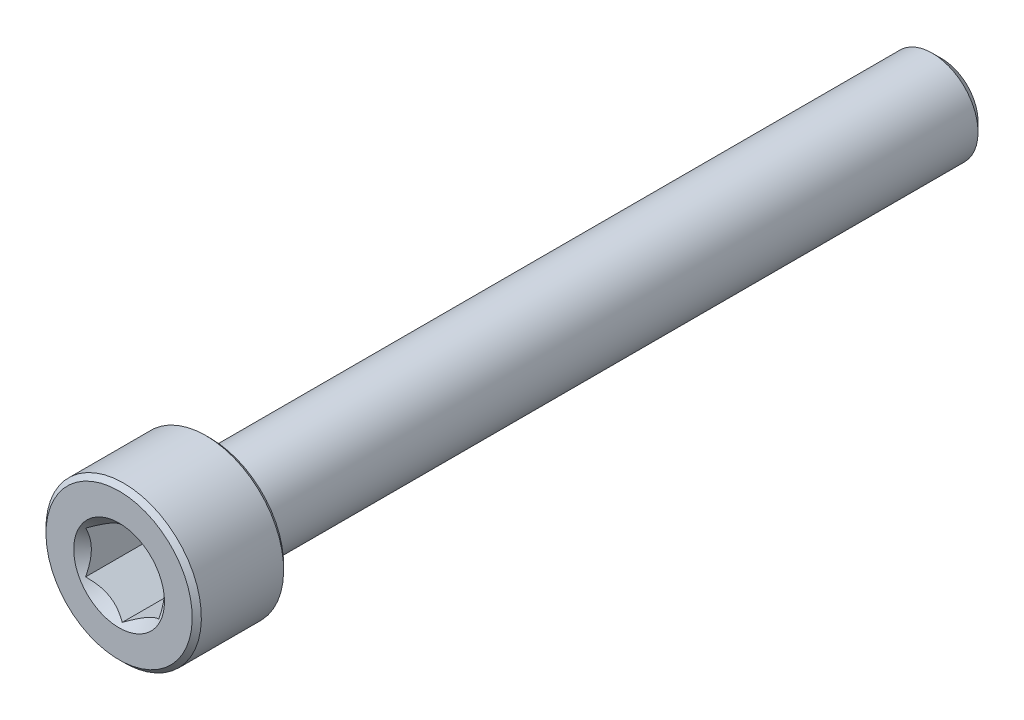
SolidWorks part; units mm, degrees
ref_plane "Front Plane" through (0, 0, 0) normal (0, 0, 1) x (1, 0, 0)
ref_plane "Top Plane" through (0, 0, 0) normal (0, 1, 0) x (1, 0, 0)
ref_plane "Right Plane" through (0, 0, 0) normal (1, 0, 0) x (0, 0, -1)
sketch "Sketch1" plane through (0, 0, 0) normal (1, 0, 0) x (0, 0, -1)
  line L0 (-22.5, 0) -> (22.5, 0) construction
  line L1 (22.5, 0) -> (22.5, 1.9804) construction
  line L2 (22.5, 1.9804) -> (21.9804, 2.5) construction
  line L3 (21.9804, 2.5) -> (21.9, 2.5) construction
  line L4 (21.9, 2.5) -> (-17.5, 2.5) construction
  line L5 (-17.5, 2.5) -> (-17.5, 4.25) construction
  line L6 (-17.5, 4.25) -> (-22.5, 4.25) construction
  line L7 (-22.5, 4.25) -> (-22.5, 0) construction
  line L8 (22.5, 1.9804) -> (22.5, 2.5) construction
  line L9 (22.45, 2.5866) -> (22.85, 1.8938) construction
  line L10 (22.85, 1.8938) -> (23.25, 2.5866) construction
  line L11 (23.25, 2.5866) -> (22.45, 2.5866) construction
  line L12 (22.85, 2.5866) -> (22.85, 2.5) construction
  line L13 (22.85, 1.8938) -> (22.85, 1.9804) construction
  line L14 (22.8, 1.9804) -> (22.9, 1.9804) construction
  line L15 (22.5, 2.5) -> (23.2, 2.5) construction
  line L16 (22.475, 2.5433) -> (23.225, 2.5433) construction
  line L17 (22.5, 0) -> (22.5, -2.5) construction
  line L18 (-17.75, 4.25) -> (-17.5, 4) construction
  line L19 (-22.25, 4.25) -> (-22.5, 4) construction
  line L20 (-17.5, 2.5) -> (-17.5, 0) construction
  line L21 (-17.5, 1.25) -> (-4.1667, 1.25) construction
  line L22 (-4.1667, 1.25) -> (9.1667, 1.25) construction
  line L23 (9.1667, 1.25) -> (22.5, 1.25) construction
  line L24 (-4.1667, 1.25) -> (-4.1667, 2.5) construction
  line L25 (-4.1667, 2.5) -> (-4.1667, 4.25) construction
  line L26 (9.1667, 1.25) -> (9.1667, 4.25) construction
  point P0 (-22.5, 2)
  point P3 (20.5, 2.5)
  point P4 (0, 0)
  point P18 (9.1667, 2.5)
  point P22 (22.85, 1.9804)
  point P24 (21.9, 2.5)
  point P25 (22.85, 2.5)
  point P28 (22.85, 2.5433)
  point P29 (20.5, -2.5)
  point P30 (-4.1667, 2.5)
  point P31 (-20, 4.25)
  point P37 (-18.375, 4.25)
  point P38 (-22.125, 4.25)
  point P45 (-4.1667, 1.25)
  point P46 (9.1667, 1.25)
  dimension "D2" = 0.1
  dimension "D7" = 0.25
  dimension "D8" = 0.25
  dimension "D9" = 0.25
  dimension "D10" = 0.125
  dimension "D11" = 0.625
  dimension "Drive Size" = 4
  dimension "Head Diameter" = 8.5
  dimension "Head Height" = 5
  dimension "Thread Pitch" = 0.8
  dimension "Thread Dia" = 5
  dimension "Length" = 40
  dimension "D12" = 0.6
  dimension "D4" = 2
  dimension "D3" = 45
sketch "Sketch2" plane through (0, 0, 0) normal (1, 0, 0) x (0, 0, -1)
  line L0 (-22.5, 0) -> (-22.5, 4)
  line L1 (-22.25, 4.25) -> (-17.75, 4.25)
  line L2 (-17.5, 4) -> (-17.5, 2.75)
  line L4 (21.9804, 2.5) -> (22.5, 1.9804)
  line L5 (22.5, 1.9804) -> (22.5, 0)
  line L6 (-17.5, 4.25) -> (-22.5, 4.25) construction
  line L7 (22.5, 0) -> (-22.5, 0)
  line L8 (-22.25, 4.25) -> (-22.5, 4) construction
  line L10 (-22.25, 4.25) -> (-22.5, 4)
  line L14 (-17.75, 4.25) -> (-17.5, 4) construction
  line L16 (-17.75, 4.25) -> (-17.5, 4)
  line L17 (-17.5, 2.5) -> (-17.5, 4.25) construction
  line L19 (-17.25, 2.5) -> (21.9804, 2.5)
  line L20 (21.9, 2.5) -> (-17.5, 2.5) construction
  arc A1 (-17.5, 2.75) -> (-17.25, 2.5) centre (-17.25, 2.75) ccw
  dimension "D3" = 0.25
revolve "Revolve1" add sketch "Sketch2" angle 360 about L7
sketch "Sketch3" plane through (0, 0, 22.5) normal (0, 0, 1) x (1, 0, 0)
  line L1 (2, -1.1547) -> (2, 1.1547)
  line L2 (2, 1.1547) -> (0, 2.3094)
  line L3 (0, 2.3094) -> (-2, 1.1547)
  line L4 (-2, 1.1547) -> (-2, -1.1547)
  line L5 (-2, -1.1547) -> (0, -2.3094)
  line L6 (0, -2.3094) -> (2, -1.1547)
  circle A0 centre (0, 0) radius 2 construction
  circle A1 centre (0, 0) radius 4.25 construction
  circle A2 centre (0, 0) radius 4.25 construction
  circle A3 centre (0, 0) radius 2.3094 construction
  point P13 (0, 0)
  dimension "D1" = 4.6188
extrude "Cut-Extrude1" cut sketch "Sketch3" against normal offset from surface (4 mm away) 1 up to face at (0, 4, 17.5)
sketch "Sketch4" plane through (0, 0, 22.5) normal (0, 0, 1) x (1, 0, 0)
  circle A0 centre (0, 0) radius 2.4826
  dimension "D1" = 4.9652
extrude "Cut-Extrude2" cut sketch "Sketch4" against normal up to vertex (2.5 mm away) draft 45 up to point (0, 4.25, 20)
sketch "Sketch11" plane through (0, 0, 0) normal (1, 0, 0) x (0, 0, -1)
  line L0 (-22.5, 0) -> (22.5, 0) construction
  line L1 (-22.5, 0) -> (22.5, 0) construction
  line L2 (-10, 0) -> (-10, 2.5) construction
  line L3 (21.9, 2.5) -> (-17.5, 2.5) construction
  line L4 (15, 0) -> (15, 2.5) construction
  line L6 (22.5, 1.9804) -> (22.5, 2.5) construction
  point P2 (-10, 0)
  point P3 (15, 0)
  dimension "D1" = 7.5
  dimension "D2" = 7.5
sketch "Sketch6" [suppressed] plane through (0, 0, -15) normal (0, 0, -1) x (-1, 0, 0)
  circle A0 centre (0, 0) radius 2.5
curve "Helix/Spiral1" [suppressed]
sketch "Sketch10" [suppressed] plane through (0, 0, 0) normal (1, 0, 0) x (0, 0, -1)
  line L0 (-9.75, -4.25) -> (-9.75, 4.25)
  line L5 (-15, 0) -> (15, 0) construction
  line L6 (-9.75, 2.5) -> (-9.75, -2.5) construction
  point P3 (-9.75, 0)
split "Split1" [suppressed] bodies to split 106
sketch "Sketch7" [suppressed] plane through (0, 0, 0) normal (1, 0, 0) x (0, 0, -1)
  line L0 (14.975, 2.5433) -> (15.725, 2.5433)
  line L1 (15.725, 2.5433) -> (15.4, 1.9804)
  line L2 (15.4, 1.9804) -> (15.3, 1.9804)
  line L3 (15.3, 1.9804) -> (14.975, 2.5433)
sweep "Cut-Sweep1" [suppressed] cut profiles "Sketch7" path "Helix/Spiral1"
sketch "Sketch8" [suppressed] plane through (0, 0, 0) normal (1, 0, 0) x (0, 0, -1)
  line L0 (-10, 0) -> (-10, 2.5)
  line L1 (-9.75, -2.5) -> (-9.75, 2.5) construction
  line L2 (-10, 2.5) -> (-9.75, 2.5)
  line L4 (-9.75, 2.5) -> (-8.3066, 0)
  line L5 (-8.3066, 0) -> (-10, 0)
  line L6 (14.4, 2.5) -> (-10, 2.5) construction
  line L7 (-15, 0) -> (15, 0) construction
  dimension "D1" = 60
revolve "Revolve2" [suppressed] add sketch "Sketch8" angle 360 about L5
equation "\"D2@Sketch1\" = \"Thread Pitch@Sketch1\" / 8"
equation "\"D4@Helix/Spiral1\" = \"Thread Pitch@Sketch1\""
equation "\"D7@Sketch1\" = \"Head Height@Sketch1\" * .05"
equation "\"D8@Sketch1\"=\"D7@Sketch1\""
equation "\"D9@Sketch1\"=\"D7@Sketch1\""
equation "\"D10@Sketch1\"=\"D7@Sketch1\"/2"
equation "\"D11@Sketch1\"=\"D10@Sketch1\"*5"
equation "\"D4@Sketch1\"=\"Thread Pitch@Sketch1\"*2.5"
equation "\"D12@Sketch1\"=\"Thread Pitch@Sketch1\"*.75"
equation "\"D3@Helix/Spiral1\"=\"Length@Sketch1\"+\"Thread Pitch@Sketch1\""
equation "\"D3@Sketch2\"=\"Thread Dia@Sketch1\"*0.05"
equation "\"D1@Sketch11\"=\"Length@Sketch1\"*0.1875"
equation "\"D2@Sketch11\"=\"D1@Sketch11\""
equation "\"D1@Sketch4\"=\"D1@Sketch3\"*1.075"
